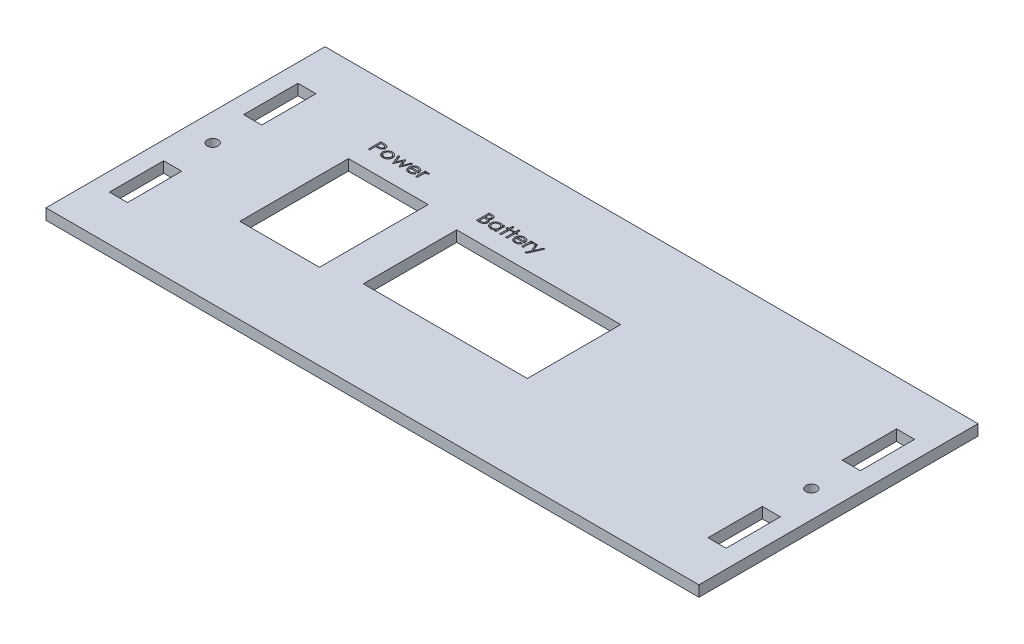
SolidWorks part; units mm, degrees
material "PMMA"
ref_plane "Front Plane" through (0, 0, 0) normal (0, 0, 1) x (1, 0, 0)
ref_plane "Top Plane" through (0, 0, 0) normal (0, 1, 0) x (1, 0, 0)
ref_plane "Right Plane" through (0, 0, 0) normal (1, 0, 0) x (0, 0, -1)
sketch "Schizzo1" plane through (0, 0, 0) normal (0, 1, 0) x (1, 0, 0)
  line L0 (-90.17, -38.535) -> (90.17, 38.535) construction
  line L1 (-90.17, 38.535) -> (90.17, 38.535)
  line L2 (-90.17, 38.535) -> (-90.17, -38.535)
  line L3 (-90.17, -38.535) -> (90.17, -38.535)
  line L4 (90.17, 38.535) -> (90.17, -38.535)
  point P4 (0, 0)
  dimension "D1" = 77.07
  dimension "D2" = 180.34
extrude "Estrusione-Estrusione1" add sketch "Schizzo1" along normal blind 3
sketch "Schizzo2" plane through (0, 0, 0) normal (0, 1, 0) x (1, 0, 0)
  line L0 (-90.17, 38.535) -> (-90.17, -38.535) construction
  line L1 (-85.17, 26.035) -> (-80.17, 26.035)
  line L2 (-85.17, 26.035) -> (-85.17, 11.035)
  line L3 (-85.17, 11.035) -> (-80.17, 11.035)
  line L4 (-80.17, 26.035) -> (-80.17, 11.035)
  line L5 (90.17, 38.535) -> (-90.17, 38.535) construction
  line L6 (-90.17, 0) -> (90.17, 0) construction
  line L7 (90.17, -38.535) -> (90.17, 38.535) construction
  line L8 (0, 38.535) -> (0, -38.535) construction
  line L9 (-90.17, -38.535) -> (90.17, -38.535) construction
  line L10 (-85.17, -26.035) -> (-85.17, -11.035)
  line L11 (-85.17, -26.035) -> (-80.17, -26.035)
  line L12 (-80.17, -26.035) -> (-80.17, -11.035)
  line L13 (-85.17, -11.035) -> (-80.17, -11.035)
  line L14 (85.17, -26.035) -> (85.17, -11.035)
  line L15 (85.17, -11.035) -> (80.17, -11.035)
  line L16 (80.17, -26.035) -> (80.17, -11.035)
  line L17 (85.17, -26.035) -> (80.17, -26.035)
  line L18 (85.17, 26.035) -> (85.17, 11.035)
  line L19 (85.17, 26.035) -> (80.17, 26.035)
  line L20 (80.17, 26.035) -> (80.17, 11.035)
  line L21 (85.17, 11.035) -> (80.17, 11.035)
  line L22 (-82.67, 11.035) -> (-82.67, -11.035) construction
  circle A0 centre (-82.67, 0) radius 1.5
  circle A1 centre (82.67, 0) radius 1.5
  dimension "D5" = 3
  dimension "D2" = 5
  dimension "D1" = 15
  dimension "D3" = 5
  dimension "D4" = 12.5
extrude "Taglio-Estrusione1" cut sketch "Schizzo2" along direction (0, 1, 0) on the side of the normal through all
sketch "Schizzo3" plane through (0, 0, 0) normal (0, 1, 0) x (1, 0, 0)
  line L0 (-90.17, 0) -> (90.17, 0) construction
  line L1 (-28.17, 12.9) -> (17.13, 12.9)
  line L2 (-28.17, 12.9) -> (-28.17, -12.9)
  line L3 (-28.17, -12.9) -> (17.13, -12.9)
  line L4 (17.13, 12.9) -> (17.13, -12.9)
  line L5 (-90.17, 38.535) -> (-90.17, -38.535) construction
  line L6 (90.17, -38.535) -> (90.17, 38.535) construction
  line L8 (-60.17, 15) -> (-38.17, 15)
  line L9 (-60.17, 15) -> (-60.17, -15)
  line L10 (-60.17, -15) -> (-38.17, -15)
  line L11 (-38.17, 15) -> (-38.17, -15)
  point P4 (-28.17, 0)
  point P15 (-38.17, 0)
  dimension "D1" = 45.3
  dimension "D2" = 25.8
  dimension "D3" = 10
  dimension "D4" = 22
  dimension "D5" = 30
  dimension "D6" = 30
extrude "Taglio-Estrusione2" cut sketch "Schizzo3" along direction (0, 1, 0) on the side of the normal through all
sketch "Schizzo4" plane through (0, 3, 0) normal (0, 1, 0) x (1, 0, 0)
  line L0 (-28.17, 12.9) -> (-28.17, -12.9) construction
  line L1 (17.13, 12.9) -> (-28.17, 12.9) construction
  text T0 "<b>Battery</b>"
  dimension "D1" = 5
extrude "Taglio-Estrusione3" cut sketch "Schizzo4" along direction (0, 1, 0) on the side against the normal blind 1
sketch "Schizzo5" plane through (0, 3, 0) normal (0, 1, 0) x (1, 0, 0)
  line L0 (-38.17, 15) -> (-60.17, 15) construction
  line L1 (-60.17, 15) -> (-60.17, 20) construction
  text T0 "<b>Power</b>"
  dimension "D1" = 5
extrude "Taglio-Estrusione4" cut sketch "Schizzo5" against normal blind 1
equation "\"Thickness5\"= 5"
equation "\"D1@Estrusione-Estrusione1\"=\"Thickness3\""
equation "\"D2@Schizzo2\"= \"Thickness5\""
equation "\"D3@Schizzo2\"=\"Thickness5\""
equation "\"Thickness3\"= 3"
